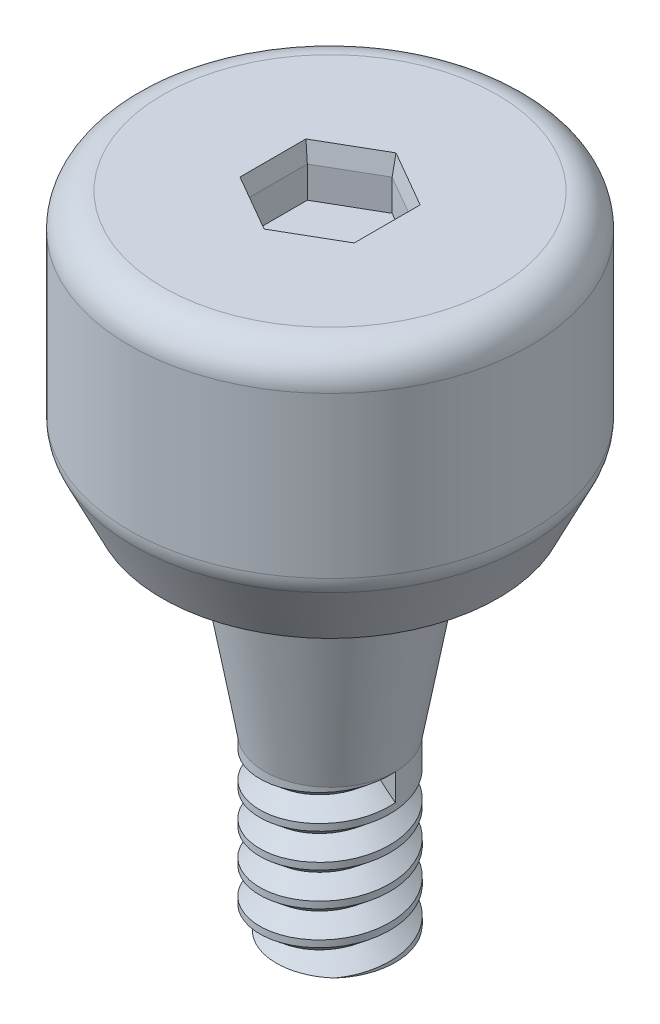
SolidWorks part; units mm, degrees
ref_plane "Plan de face" through (0, 0, 0) normal (0, 0, 1) x (1, 0, 0)
ref_plane "Plan de dessus" through (0, 0, 0) normal (0, 1, 0) x (1, 0, 0)
ref_plane "Plan de droite" through (0, 0, 0) normal (1, 0, 0) x (0, 0, -1)
sketch "Esquisse1" plane through (0, 0, 0) normal (0, 0, 1) x (1, 0, 0)
  line L0 (-3, 0) -> (-1.942, -6)
  line L1 (-3, 0) -> (-5, 0)
  line L2 (0, 0) -> (0, 2)
  line L5 (-1.942, -6) -> (-1.942, -11)
  line L6 (-1.942, -11) -> (0, -11)
  line L7 (0, -11) -> (0, 0)
  line L8 (-5.8688, 1.7935) -> (-5, 0)
  line L10 (0, 2) -> (0, 8)
  line L11 (0, 8) -> (-5.9689, 8)
  line L12 (-5.9689, 2.2295) -> (-5.9689, 8)
  arc A0 (-5.8688, 1.7935) -> (-5.9689, 2.2295) centre (-4.9689, 2.2295) cw
  dimension "D2" = 1
  dimension "D1" = 8
  dimension "D3" = 3
  dimension "D4" = 80
  dimension "D5" = 6
  dimension "D6" = 5
  dimension "D7" = 5.9689
revolve "Révolution1" add sketch "Esquisse1" angle 360 about L7
ref_plane "Plan1" through (0, -6, 0) normal (0, 1, 0) x (1, 0, 0)
sketch "Esquisse2" plane through (0, -6, 0) normal (0, 1, 0) x (1, 0, 0)
  circle A0 centre (0, 0) radius 1.95
curve "Hélice/Spirale1" pitch 1 height 5 radius 1.95 centre (0, -6, 0) axis (0, -1, 0) start towards (1, 0, 0)
sketch "Esquisse3" plane through (0, 0, 0) normal (0, 0, 1) x (1, 0, 0)
  line L0 (1.942, -6) -> (1.942, -6.8)
  line L1 (2.1362, -6) -> (-2.1362, -6) construction
  line L2 (1.942, -11) -> (1.942, -6) construction
  line L5 (1.452, -6.4) -> (1.942, -6)
  line L6 (1.942, -6.8) -> (1.452, -6.4)
  dimension "D1" = 0.8
sketch "Esquisse4" plane through (0, 0, 0) normal (0, 0, 1) x (1, 0, 0)
  line L0 (0, -10.8604) -> (0, -12.4734) construction
  line L2 (0, -12.0701) -> (3.2929, -12.0701)
  line L3 (0, -12.0701) -> (0, -10.9164)
  line L4 (0, -10.9164) -> (3.2929, -10.9164)
  line L5 (3.2929, -12.0701) -> (3.2929, -10.9164)
revolve "Enlèvement de matière-Révolution1" cut sketch "Esquisse4" angle 360 about L0
sketch "Esquisse6" plane through (0, 8, 0) normal (0, 1, 0) x (1, 0, 0)
  line L1 (0, 1.8475) -> (-1.6, 0.9238)
  line L2 (-1.6, 0.9238) -> (-1.6, -0.9238)
  line L3 (-1.6, -0.9238) -> (0, -1.8475)
  line L4 (0, -1.8475) -> (1.6, -0.9238)
  line L5 (1.6, -0.9238) -> (1.6, 0.9238)
  line L6 (1.6, 0.9238) -> (0, 1.8475)
  circle A0 centre (0, 0) radius 1.6 construction
extrude "Enlèv. mat.-Extru.2" cut sketch "Esquisse6" against normal blind 1.5
chamfer "Chanfrein2" distance 0.1 angle 80 6 edges at (0.8, 8, -1.3856) (1.6, 8, 0) (0.8, 8, 1.3856) (-0.8, 8, 1.3856) (-1.6, 8, 0) (-0.8, 8, -1.3856) first distance on face at (0, 8, 0)
fillet "Congé2" radius 1 1 edges at (0, 8, -5.9689)
sweep "Enlèvement de matière-Balayage1" cut profiles "Esquisse3" path "Hélice/Spirale1"
